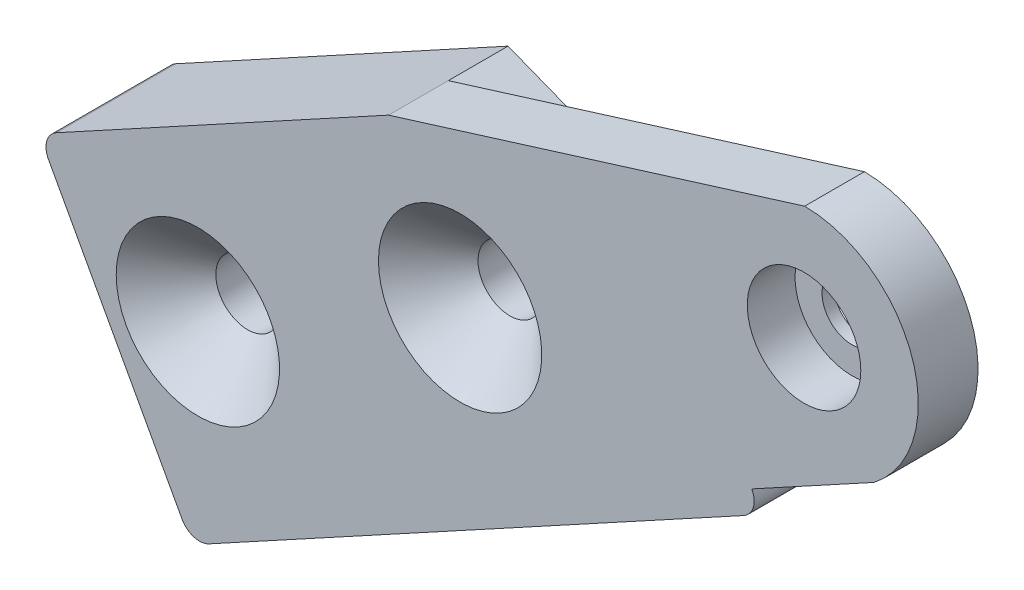
SolidWorks part; units mm, degrees
ref_plane "Front Plane" through (0, 0, 0) normal (0, 0, 1) x (1, 0, 0)
ref_plane "Top Plane" through (0, 0, 0) normal (0, 1, 0) x (1, 0, 0)
ref_plane "Right Plane" through (0, 0, 0) normal (1, 0, 0) x (0, 0, -1)
sketch "Sketch2" plane through (0, 0, 0) normal (0, 0, 1) x (1, 0, 0)
  line L0 (110.8747, 169.3007) -> (232.868, 168.0195) construction
  line L1 (231.4782, 167.9235) -> (111.8685, 169.7952)
  line L2 (109.9284, 170.22) -> (90.3522, 178.8568)
  line L3 (88.0797, 180.8644) -> (81.6243, 191.6546)
  line L4 (91.1154, 198.8867) -> (104.3747, 187.2622)
  line L5 (107.6071, 186.0223) -> (189.9391, 184.9726)
  line L6 (192.2834, 185.5226) -> (216.6587, 198.016)
  line L7 (218.9657, 198.5663) -> (266.2136, 198.3172)
  line L8 (233.9522, 168.5343) -> (269.7006, 188.0491)
  arc A0 (266.2136, 198.3172) -> (269.7006, 188.0491) centre (266.1834, 192.5808) cw
  arc A1 (81.6243, 191.6546) -> (91.1154, 198.8867) centre (86.7764, 194.737) cw
  circle A2 centre (91.5684, 182.2893) radius 1.1478 construction
  circle A3 centre (86.7764, 194.737) radius 1.0668 construction
  circle A4 centre (232.1221, 192.0862) radius 0.8742 construction
  circle A5 centre (266.1834, 192.5808) radius 1.1755 construction
  arc A6 (189.9391, 184.9726) -> (192.2834, 185.5226) centre (190.0028, 189.9722) ccw
  arc A7 (216.6587, 198.016) -> (218.9657, 198.5663) centre (218.9393, 193.5664) cw
  arc A8 (233.9522, 168.5343) -> (231.4782, 167.9235) centre (231.5564, 172.9229) cw
  arc A9 (109.9284, 170.22) -> (111.8685, 169.7952) centre (111.9467, 174.7946) ccw
  arc A10 (107.6071, 186.0223) -> (104.3747, 187.2622) centre (107.6709, 191.0219) cw
  arc A11 (90.3522, 178.8568) -> (88.0797, 180.8644) centre (92.3704, 183.4313) cw
  circle A12 centre (245.4018, 191.4665) radius 0.7725 construction
  circle A13 centre (245.2646, 181.5408) radius 0.6658 construction
  circle A14 centre (208.1864, 183.5188) radius 1.0221 construction
  circle A15 centre (86.7764, 194.737) radius 1.5
  circle A16 centre (91.5684, 182.2893) radius 2
  circle A17 centre (208.1864, 183.5188) radius 1.5
  circle A18 centre (232.1221, 192.0862) radius 1.5
  circle A20 centre (266.1834, 192.5808) radius 2
  dimension "D2" = 4
  dimension "D3" = 3
  dimension "D4" = 3
  dimension "D5" = 4
  dimension "D6" = 3
  dimension "D1" = 122
sketch "Sketch4" plane through (0, 0, 0) normal (0, 0, 1) x (1, 0, 0)
  line L0 (263.5565, 184.6951) -> (228.2317, 198.5174) construction
  line L1 (263.5565, 184.6951) -> (264.0356, 183.8173)
  line L2 (264.0356, 183.8173) -> (235.4334, 168.2035)
  line L3 (235.4334, 168.2035) -> (234.9542, 169.0813)
  line L4 (234.9542, 169.0813) -> (227.767, 182.2473)
  line L5 (227.767, 182.2473) -> (245.3217, 191.8302)
  line L6 (245.3217, 191.8302) -> (263.5565, 184.6951)
  line L7 (231.3606, 175.6643) -> (256.8427, 189.5747) construction
  line L8 (111.8685, 169.7952) -> (231.4782, 167.9235)
  line L9 (233.9522, 168.5343) -> (269.7006, 188.0491)
  line L10 (266.2136, 198.3172) -> (218.9657, 198.5663)
  line L11 (216.6587, 198.016) -> (192.2834, 185.5226)
  line L12 (189.9391, 184.9726) -> (107.6071, 186.0223)
  line L13 (104.3747, 187.2622) -> (91.1154, 198.8867)
  line L14 (81.6243, 191.6546) -> (88.0797, 180.8644)
  line L15 (90.3522, 178.8568) -> (109.9284, 170.22)
  line L16 (111.8685, 169.7952) -> (231.4782, 167.9235) construction
  line L17 (233.9522, 168.5343) -> (269.7006, 188.0491) construction
  line L18 (266.2136, 198.3172) -> (218.9657, 198.5663) construction
  line L19 (216.6587, 198.016) -> (192.2834, 185.5226) construction
  line L20 (189.9391, 184.9726) -> (107.6071, 186.0223) construction
  line L21 (104.3747, 187.2622) -> (91.1154, 198.8867) construction
  line L22 (81.6243, 191.6546) -> (88.0797, 180.8644) construction
  line L23 (90.3522, 178.8568) -> (109.9284, 170.22) construction
  circle A0 centre (235.7493, 178.06) radius 1.6
  circle A1 centre (91.5684, 182.2893) radius 2
  circle A2 centre (91.5684, 182.2893) radius 2 construction
  circle A3 centre (266.1834, 192.5808) radius 2
  circle A4 centre (266.1834, 192.5808) radius 2 construction
  circle A5 centre (232.1221, 192.0862) radius 1.5
  circle A6 centre (232.1221, 192.0862) radius 1.5 construction
  circle A7 centre (208.1864, 183.5188) radius 1.5
  circle A8 centre (208.1864, 183.5188) radius 1.5 construction
  circle A9 centre (86.7764, 194.737) radius 1.5
  circle A10 centre (86.7764, 194.737) radius 1.5 construction
  circle A11 centre (248.9153, 185.2472) radius 1.6
  arc A18 (231.4782, 167.9235) -> (233.9522, 168.5343) centre (231.5564, 172.9229) ccw
  arc A19 (269.7006, 188.0491) -> (266.2136, 198.3172) centre (266.1834, 192.5808) ccw
  arc A20 (218.9657, 198.5663) -> (216.6587, 198.016) centre (218.9393, 193.5664) ccw
  arc A21 (189.9391, 184.9726) -> (192.2834, 185.5226) centre (190.0028, 189.9722) ccw
  arc A22 (104.3747, 187.2622) -> (107.6071, 186.0223) centre (107.6709, 191.0219) ccw
  arc A23 (91.1154, 198.8867) -> (81.6243, 191.6546) centre (86.7764, 194.737) ccw
  arc A24 (88.0797, 180.8644) -> (90.3522, 178.8568) centre (92.3704, 183.4313) ccw
  arc A25 (109.9284, 170.22) -> (111.8685, 169.7952) centre (111.9467, 174.7946) ccw
  arc A26 (231.4782, 167.9235) -> (233.9522, 168.5343) centre (231.5564, 172.9229) ccw construction
  arc A27 (269.7006, 188.0491) -> (266.2136, 198.3172) centre (266.1834, 192.5808) ccw construction
  arc A28 (218.9657, 198.5663) -> (216.6587, 198.016) centre (218.9393, 193.5664) ccw construction
  arc A29 (189.9391, 184.9726) -> (192.2834, 185.5226) centre (190.0028, 189.9722) ccw construction
  arc A30 (104.3747, 187.2622) -> (107.6071, 186.0223) centre (107.6709, 191.0219) ccw construction
  arc A31 (91.1154, 198.8867) -> (81.6243, 191.6546) centre (86.7764, 194.737) ccw construction
  arc A32 (88.0797, 180.8644) -> (90.3522, 178.8568) centre (92.3704, 183.4313) ccw construction
  arc A33 (109.9284, 170.22) -> (111.8685, 169.7952) centre (111.9467, 174.7946) ccw construction
  dimension "D12" = 3.2
  dimension "D13" = 3.2
  dimension "D7" = 1
  dimension "D8" = 15
  dimension "D9" = 7
  dimension "D10" = 50
  dimension "D11" = 20
  dimension "D14" = 5
  dimension "D15" = 15
  dimension "D1" = 0
  dimension "D2" = 0
  dimension "D3" = 0
  dimension "D4" = 0
  dimension "D5" = 0
  dimension "D6" = 0
extrude "Boss-Extrude1" add sketch "Sketch4" along normal blind 3
sketch "Sketch5" plane through (0, 0, 0) normal (0, 0, -1) x (-1, 0, 0)
  line L0 (-263.5565, 184.6951) -> (-264.0356, 183.8173)
  line L1 (-264.0356, 183.8173) -> (-235.4334, 168.2035)
  line L2 (-227.767, 182.2473) -> (-235.4334, 168.2035) construction
  line L3 (-235.4334, 168.2035) -> (-264.0356, 183.8173) construction
  line L4 (-235.4334, 168.2035) -> (-234.9542, 169.0813)
  line L5 (-234.9542, 169.0813) -> (-263.5565, 184.6951)
  line L8 (-231.4782, 167.9235) -> (-111.8685, 169.7952)
  line L9 (-269.7006, 188.0491) -> (-233.9522, 168.5343)
  line L10 (-218.9657, 198.5663) -> (-266.2136, 198.3172)
  line L11 (-192.2834, 185.5226) -> (-216.6587, 198.016)
  line L12 (-107.6071, 186.0223) -> (-189.9391, 184.9726)
  line L13 (-91.1154, 198.8867) -> (-104.3747, 187.2622)
  line L14 (-88.0797, 180.8644) -> (-81.6243, 191.6546)
  line L15 (-109.9284, 170.22) -> (-90.3522, 178.8568)
  line L16 (-231.4782, 167.9235) -> (-111.8685, 169.7952) construction
  line L17 (-269.7006, 188.0491) -> (-233.9522, 168.5343) construction
  line L18 (-218.9657, 198.5663) -> (-266.2136, 198.3172) construction
  line L19 (-192.2834, 185.5226) -> (-216.6587, 198.016) construction
  line L20 (-107.6071, 186.0223) -> (-189.9391, 184.9726) construction
  line L21 (-91.1154, 198.8867) -> (-104.3747, 187.2622) construction
  line L22 (-88.0797, 180.8644) -> (-81.6243, 191.6546) construction
  line L23 (-109.9284, 170.22) -> (-90.3522, 178.8568) construction
  circle A1 centre (-91.5684, 182.2893) radius 2
  circle A2 centre (-91.5684, 182.2893) radius 2 construction
  circle A3 centre (-266.1834, 192.5808) radius 2
  circle A4 centre (-266.1834, 192.5808) radius 2 construction
  circle A5 centre (-232.1221, 192.0862) radius 1.5
  circle A6 centre (-232.1221, 192.0862) radius 1.5 construction
  circle A7 centre (-208.1864, 183.5188) radius 1.5
  circle A8 centre (-208.1864, 183.5188) radius 1.5 construction
  circle A9 centre (-86.7764, 194.737) radius 1.5
  circle A10 centre (-86.7764, 194.737) radius 1.5 construction
  arc A18 (-233.9522, 168.5343) -> (-231.4782, 167.9235) centre (-231.5564, 172.9229) ccw
  arc A19 (-266.2136, 198.3172) -> (-269.7006, 188.0491) centre (-266.1834, 192.5808) ccw
  arc A20 (-216.6587, 198.016) -> (-218.9657, 198.5663) centre (-218.9393, 193.5664) ccw
  arc A21 (-192.2834, 185.5226) -> (-189.9391, 184.9726) centre (-190.0028, 189.9722) ccw
  arc A22 (-107.6071, 186.0223) -> (-104.3747, 187.2622) centre (-107.6709, 191.0219) ccw
  arc A23 (-81.6243, 191.6546) -> (-91.1154, 198.8867) centre (-86.7764, 194.737) ccw
  arc A24 (-90.3522, 178.8568) -> (-88.0797, 180.8644) centre (-92.3704, 183.4313) ccw
  arc A25 (-111.8685, 169.7952) -> (-109.9284, 170.22) centre (-111.9467, 174.7946) ccw
  arc A26 (-233.9522, 168.5343) -> (-231.4782, 167.9235) centre (-231.5564, 172.9229) ccw construction
  arc A27 (-266.2136, 198.3172) -> (-269.7006, 188.0491) centre (-266.1834, 192.5808) ccw construction
  arc A28 (-216.6587, 198.016) -> (-218.9657, 198.5663) centre (-218.9393, 193.5664) ccw construction
  arc A29 (-192.2834, 185.5226) -> (-189.9391, 184.9726) centre (-190.0028, 189.9722) ccw construction
  arc A30 (-107.6071, 186.0223) -> (-104.3747, 187.2622) centre (-107.6709, 191.0219) ccw construction
  arc A31 (-81.6243, 191.6546) -> (-91.1154, 198.8867) centre (-86.7764, 194.737) ccw construction
  arc A32 (-90.3522, 178.8568) -> (-88.0797, 180.8644) centre (-92.3704, 183.4313) ccw construction
  arc A33 (-111.8685, 169.7952) -> (-109.9284, 170.22) centre (-111.9467, 174.7946) ccw construction
  dimension "D1" = 0
  dimension "D2" = 0
  dimension "D3" = 0
  dimension "D4" = 0
  dimension "D5" = 0
  dimension "D6" = 0
extrude "Boss-Extrude2" add sketch "Sketch5" along normal blind 1.4
sketch "Sketch6" plane through (0, 0, 3) normal (0, 0, 1) x (1, 0, 0)
  line L0 (234.9542, 169.0813) -> (269.7006, 188.0491) construction
  line L1 (227.767, 182.2473) -> (257.291, 198.3642)
  line L3 (245.3217, 191.8302) -> (227.767, 182.2473) construction
  line L4 (257.291, 198.3642) -> (266.2136, 198.3172)
  line L5 (227.767, 182.2473) -> (234.9542, 169.0813)
  line L6 (234.9542, 169.0813) -> (235.4334, 168.2035)
  line L7 (235.4334, 168.2035) -> (264.0356, 183.8173)
  line L8 (111.8685, 169.7952) -> (231.4782, 167.9235)
  line L9 (233.9522, 168.5343) -> (269.7006, 188.0491)
  line L10 (266.2136, 198.3172) -> (218.9657, 198.5663)
  line L11 (216.6587, 198.016) -> (192.2834, 185.5226)
  line L12 (189.9391, 184.9726) -> (107.6071, 186.0223)
  line L13 (104.3747, 187.2622) -> (91.1154, 198.8867)
  line L14 (81.6243, 191.6546) -> (88.0797, 180.8644)
  line L15 (90.3522, 178.8568) -> (109.9284, 170.22)
  line L16 (111.8685, 169.7952) -> (231.4782, 167.9235) construction
  line L17 (233.9522, 168.5343) -> (269.7006, 188.0491) construction
  line L18 (266.2136, 198.3172) -> (218.9657, 198.5663) construction
  line L19 (216.6587, 198.016) -> (192.2834, 185.5226) construction
  line L20 (189.9391, 184.9726) -> (107.6071, 186.0223) construction
  line L21 (104.3747, 187.2622) -> (91.1154, 198.8867) construction
  line L22 (81.6243, 191.6546) -> (88.0797, 180.8644) construction
  line L23 (90.3522, 178.8568) -> (109.9284, 170.22) construction
  line L24 (264.0356, 183.8173) -> (263.5565, 184.6951)
  line L25 (269.7006, 188.0491) -> (263.5565, 184.6951)
  arc A0 (266.2136, 198.3172) -> (269.7006, 188.0491) centre (266.1834, 192.5808) cw
  circle A1 centre (91.5684, 182.2893) radius 2
  circle A2 centre (91.5684, 182.2893) radius 2 construction
  circle A3 centre (266.1834, 192.5808) radius 2
  circle A4 centre (266.1834, 192.5808) radius 2 construction
  circle A5 centre (232.1221, 192.0862) radius 1.5
  circle A6 centre (232.1221, 192.0862) radius 1.5 construction
  circle A7 centre (208.1864, 183.5188) radius 1.5
  circle A8 centre (208.1864, 183.5188) radius 1.5 construction
  circle A9 centre (86.7764, 194.737) radius 1.5
  circle A10 centre (86.7764, 194.737) radius 1.5 construction
  circle A11 centre (248.9153, 185.2472) radius 1.6 construction
  circle A12 centre (235.7493, 178.06) radius 1.6 construction
  circle A13 centre (248.9153, 185.2472) radius 1.6
  circle A14 centre (235.7493, 178.06) radius 1.6
  arc A18 (231.4782, 167.9235) -> (233.9522, 168.5343) centre (231.5564, 172.9229) ccw
  arc A19 (269.7006, 188.0491) -> (266.2136, 198.3172) centre (266.1834, 192.5808) ccw
  arc A20 (218.9657, 198.5663) -> (216.6587, 198.016) centre (218.9393, 193.5664) ccw
  arc A21 (189.9391, 184.9726) -> (192.2834, 185.5226) centre (190.0028, 189.9722) ccw
  arc A22 (104.3747, 187.2622) -> (107.6071, 186.0223) centre (107.6709, 191.0219) ccw
  arc A23 (91.1154, 198.8867) -> (81.6243, 191.6546) centre (86.7764, 194.737) ccw
  arc A24 (88.0797, 180.8644) -> (90.3522, 178.8568) centre (92.3704, 183.4313) ccw
  arc A25 (109.9284, 170.22) -> (111.8685, 169.7952) centre (111.9467, 174.7946) ccw
  arc A26 (231.4782, 167.9235) -> (233.9522, 168.5343) centre (231.5564, 172.9229) ccw construction
  arc A27 (269.7006, 188.0491) -> (266.2136, 198.3172) centre (266.1834, 192.5808) ccw construction
  arc A28 (218.9657, 198.5663) -> (216.6587, 198.016) centre (218.9393, 193.5664) ccw construction
  arc A29 (189.9391, 184.9726) -> (192.2834, 185.5226) centre (190.0028, 189.9722) ccw construction
  arc A30 (104.3747, 187.2622) -> (107.6071, 186.0223) centre (107.6709, 191.0219) ccw construction
  arc A31 (91.1154, 198.8867) -> (81.6243, 191.6546) centre (86.7764, 194.737) ccw construction
  arc A32 (88.0797, 180.8644) -> (90.3522, 178.8568) centre (92.3704, 183.4313) ccw construction
  arc A33 (109.9284, 170.22) -> (111.8685, 169.7952) centre (111.9467, 174.7946) ccw construction
  dimension "D1" = 0
  dimension "D2" = 0
  dimension "D3" = 0
  dimension "D4" = 0
  dimension "D5" = 0
  dimension "D6" = 0
extrude "Boss-Extrude3" add sketch "Sketch6" along normal blind 3
sketch "Sketch7" plane through (0, 0, 6) normal (0, 0, 1) x (1, 0, 0)
  line L16 (111.8685, 169.7952) -> (231.4782, 167.9235)
  line L17 (233.9522, 168.5343) -> (269.7006, 188.0491)
  line L18 (266.2136, 198.3172) -> (218.9657, 198.5663)
  line L19 (216.6587, 198.016) -> (192.2834, 185.5226)
  line L20 (189.9391, 184.9726) -> (107.6071, 186.0223)
  line L21 (104.3747, 187.2622) -> (91.1154, 198.8867)
  line L22 (81.6243, 191.6546) -> (88.0797, 180.8644)
  line L23 (90.3522, 178.8568) -> (109.9284, 170.22)
  line L24 (111.8685, 169.7952) -> (231.4782, 167.9235) construction
  line L25 (233.9522, 168.5343) -> (269.7006, 188.0491) construction
  line L26 (266.2136, 198.3172) -> (218.9657, 198.5663) construction
  line L27 (216.6587, 198.016) -> (192.2834, 185.5226) construction
  line L28 (189.9391, 184.9726) -> (107.6071, 186.0223) construction
  line L29 (104.3747, 187.2622) -> (91.1154, 198.8867) construction
  line L30 (81.6243, 191.6546) -> (88.0797, 180.8644) construction
  line L31 (90.3522, 178.8568) -> (109.9284, 170.22) construction
  circle A8 centre (266.1834, 192.5808) radius 2.85
  circle A9 centre (91.5684, 182.2893) radius 2
  circle A10 centre (91.5684, 182.2893) radius 2 construction
  circle A11 centre (266.1834, 192.5808) radius 2
  circle A12 centre (266.1834, 192.5808) radius 2 construction
  circle A13 centre (232.1221, 192.0862) radius 1.5
  circle A14 centre (232.1221, 192.0862) radius 1.5 construction
  circle A15 centre (208.1864, 183.5188) radius 1.5
  circle A16 centre (208.1864, 183.5188) radius 1.5 construction
  circle A17 centre (86.7764, 194.737) radius 1.5
  circle A18 centre (86.7764, 194.737) radius 1.5 construction
  arc A26 (231.4782, 167.9235) -> (233.9522, 168.5343) centre (231.5564, 172.9229) ccw
  arc A27 (269.7006, 188.0491) -> (266.2136, 198.3172) centre (266.1834, 192.5808) ccw
  arc A28 (218.9657, 198.5663) -> (216.6587, 198.016) centre (218.9393, 193.5664) ccw
  arc A29 (189.9391, 184.9726) -> (192.2834, 185.5226) centre (190.0028, 189.9722) ccw
  arc A30 (104.3747, 187.2622) -> (107.6071, 186.0223) centre (107.6709, 191.0219) ccw
  arc A31 (91.1154, 198.8867) -> (81.6243, 191.6546) centre (86.7764, 194.737) ccw
  arc A32 (88.0797, 180.8644) -> (90.3522, 178.8568) centre (92.3704, 183.4313) ccw
  arc A33 (109.9284, 170.22) -> (111.8685, 169.7952) centre (111.9467, 174.7946) ccw
  arc A34 (231.4782, 167.9235) -> (233.9522, 168.5343) centre (231.5564, 172.9229) ccw construction
  arc A35 (269.7006, 188.0491) -> (266.2136, 198.3172) centre (266.1834, 192.5808) ccw construction
  arc A36 (218.9657, 198.5663) -> (216.6587, 198.016) centre (218.9393, 193.5664) ccw construction
  arc A37 (189.9391, 184.9726) -> (192.2834, 185.5226) centre (190.0028, 189.9722) ccw construction
  arc A38 (104.3747, 187.2622) -> (107.6071, 186.0223) centre (107.6709, 191.0219) ccw construction
  arc A39 (91.1154, 198.8867) -> (81.6243, 191.6546) centre (86.7764, 194.737) ccw construction
  arc A40 (88.0797, 180.8644) -> (90.3522, 178.8568) centre (92.3704, 183.4313) ccw construction
  arc A41 (109.9284, 170.22) -> (111.8685, 169.7952) centre (111.9467, 174.7946) ccw construction
  dimension "D7" = 5.7
  dimension "D1" = 0
  dimension "D2" = 0
  dimension "D3" = 0
  dimension "D4" = 0
  dimension "D5" = 0
  dimension "D6" = 0
extrude "Cut-Extrude1" cut sketch "Sketch7" against normal blind 2.4
sketch "Sketch9" plane through (0, 0, 3) normal (0, 0, -1) x (-1, 0, 0)
  line L0 (-245.3217, 191.8302) -> (-266.2136, 198.3172)
  line L1 (-266.2136, 198.3172) -> (-257.291, 198.3642)
  line L2 (-257.291, 198.3642) -> (-245.3217, 191.8302)
extrude "Cut-Extrude2" cut sketch "Sketch9" against normal blind 4.6
sketch "Sketch10" plane through (0, 0, 3.6) normal (0, 0, 1) x (1, 0, 0)
  circle A0 centre (266.1834, 192.5808) radius 1.5
  dimension "D1" = 3
extrude "Cut-Extrude3" cut sketch "Sketch10" against normal blind 10 contours A0
chamfer "Chamfer1" distance 2.5 angle 45 2 edges at (237.3493, 178.06, 6) (250.5153, 185.2472, 6)
fillet "Fillet1" radius 1 3 edges at (264.0356, 183.8173, 2.3) (227.767, 182.2473, 3) (235.4334, 168.2035, 2.3)
